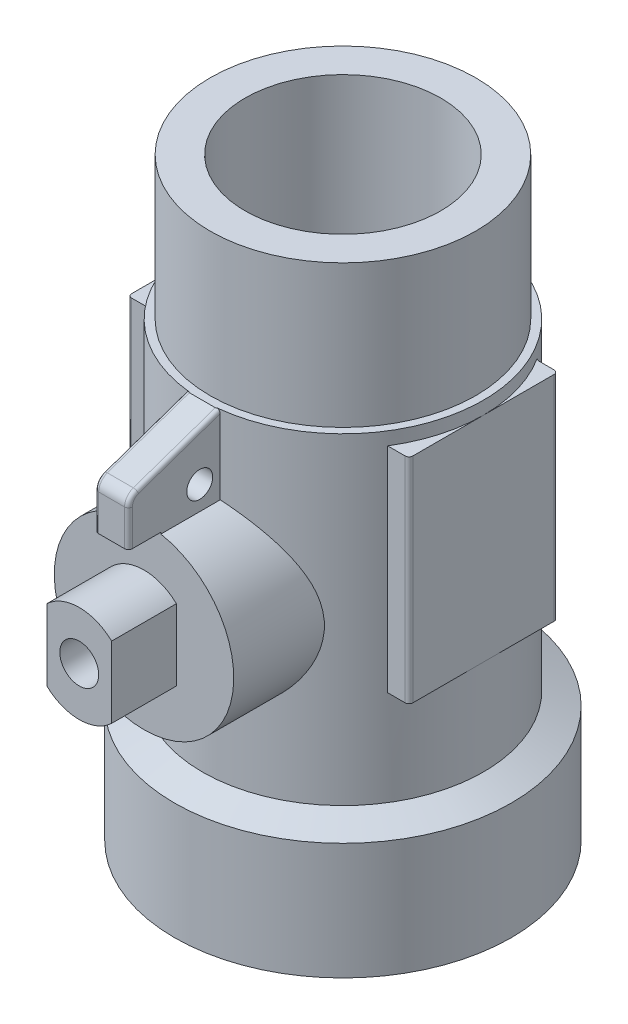
SolidWorks part; units mm, degrees
ref_plane "Front Plane" through (0, 0, 0) normal (0, 0, 1) x (1, 0, 0)
ref_plane "Top Plane" through (0, 0, 0) normal (0, 1, 0) x (1, 0, 0)
ref_plane "Right Plane" through (0, 0, 0) normal (1, 0, 0) x (0, 0, -1)
sketch "Sketch1" plane through (0, 0, 0) normal (0, 0, 1) x (1, 0, 0)
  line L0 (0, 0) -> (0, 45.85) construction
  line L1 (0, 45.85) -> (7.55, 45.85) construction
  line L2 (7.55, 45.85) -> (7.55, 33.85)
  line L3 (7.55, 33.85) -> (5, 32.85)
  line L4 (5, 32.85) -> (5, 28.85)
  line L5 (5, 28.85) -> (0, 28.85)
  line L6 (0, 28.85) -> (0, 12)
  line L7 (0, 12) -> (5, 12)
  line L8 (5, 12) -> (5, 7.7)
  line L9 (5, 7.7) -> (9, 7.7)
  line L10 (9, 7.7) -> (9, 0)
  line L11 (9, 0) -> (13, 0)
  line L12 (13, 0) -> (13, 9)
  line L13 (13, 9) -> (10.85, 10)
  line L16 (10.85, 10) -> (10.85, 34.85)
  line L20 (10.25, 34.85) -> (10.25, 45.85)
  line L21 (10.25, 45.85) -> (7.55, 45.85)
  line L22 (10.85, 34.85) -> (10.25, 34.85)
  point P13 (0, 0)
  point P18 (10.85, 10.0199)
  point P19 (0, 0)
  dimension "D1" = 45.85
  dimension "D2" = 12
  dimension "D3" = 13
  dimension "D4" = 17
  dimension "D5" = 10.25
  dimension "D6" = 2.7
  dimension "D7" = 5
  dimension "D8" = 11
  dimension "D9" = 8
  dimension "D10" = 1
  dimension "D11" = 13
  dimension "D12" = 4
  dimension "D14" = 7.7
  dimension "D15" = 12
  dimension "D16" = 10.85
  dimension "D17" = 9
revolve "Revolve1" add sketch "Sketch1" angle 360 about L0
ref_plane "Plane1" through (10.85, 0, 0) normal (1, 0, 0) x (0, 1, 0)
sketch "Sketch2" plane through (10.85, 0, 0) normal (1, 0, 0) x (0, 1, 0)
  line L1 (33.85, 5.75) -> (17.35, 5.75)
  line L2 (33.85, 5.75) -> (33.85, -5.75)
  line L3 (33.85, -5.75) -> (17.35, -5.75)
  line L4 (17.35, 5.75) -> (17.35, -5.75)
  line L5 (34.85, -10.85) -> (34.85, 10.85) construction
  point P4 (0, 0)
  point P7 (0, 0)
  point P8 (0, 0)
  point P10 (0, 0)
  point P12 (17.35, 0)
  dimension "D1" = 1
  dimension "D2" = 16.5
  dimension "D3" = 11.5
extrude "Boss-Extrude1" add sketch "Sketch2" against normal blind 2
mirror "Mirror1" about plane through (0, 0, 0) normal (1, 0, 0) of "Boss-Extrude1"
ref_plane "Plane2" through (0, 0, 10.85) normal (0, 0, 1) x (0, -1, 0)
sketch "Sketch3" plane through (0, 0, 10.85) normal (0, 0, 1) x (0, -1, 0)
  line L0 (0, -13) -> (0, 13) construction
  circle A0 centre (-22, 0) radius 6.925
  dimension "D1" = 13.85
  dimension "D2" = 22
extrude "Boss-Extrude2" add sketch "Sketch3" along normal blind 4.5 and the other way blind 3
sketch "Sketch4" plane through (0, 0, 0) normal (1, 0, 0) x (0, 0, -1)
  line L12 (-10.85, 34.85) -> (-17.85, 32.425)
  line L13 (-17.85, 32.425) -> (-17.85, 28.925)
  line L14 (-17.85, 28.925) -> (-15.35, 28.925)
  line L15 (-15.35, 28.925) -> (-15.35, 27.925)
  line L16 (-15.35, 27.925) -> (-10.25, 27.925)
  line L20 (-10.85, 34.85) -> (-10.25, 34.85)
  line L21 (-10.25, 34.85) -> (-10.25, 27.925)
  line L23 (10.85, 34.85) -> (-10.85, 34.85) construction
  line L24 (10.25, 34.85) -> (-10.25, 34.85) construction
  circle A0 centre (-12.35, 30.625) radius 1
  point P0 (-11.1968, 34.85)
  dimension "D6" = 2
  dimension "D1" = 2.5
  dimension "D2" = 3.5
  dimension "D3" = 1
  dimension "D4" = 2.7
  dimension "D5" = 2.1
extrude "Boss-Extrude6" add sketch "Sketch4" along normal blind 1.3 and the other way blind 1.3
fillet "Fillet2" radius 0.3 1 edges at (-9.2011, 25.6, 5.75)
fillet "Fillet4" radius 0.3 1 edges at (10.85, 25.6, 5.75)
fillet "Fillet7" radius 0.3 1 edges at (10.85, 25.6, -5.75)
fillet "Fillet8" radius 0.3 1 edges at (-10.85, 25.6, -5.75)
fillet "Fillet9" radius 0.3 1 edges at (-10.85, 25.6, 5.75)
fillet "Fillet10" radius 0.3 4 edges at (1.3, 30.675, 17.85) (-1.3, 33.6375, 14.35) (-1.3, 30.675, 17.85) (1.3, 33.6375, 14.35)
fillet "Fillet11" radius 0.3 1 edges at (9.2011, 25.6, -5.75)
fillet "Fillet12" radius 0.3 1 edges at (-9.2011, 25.6, -5.75)
sketch "Sketch5" plane through (0, 0, 15.35) normal (0, 0, 1) x (1, 0, 0)
  line L0 (-2.5, 19.25) -> (-2.5, 24.75)
  line L1 (2.5, 19.25) -> (2.5, 24.75)
  line L2 (-6.925, 22) -> (6.925, 22) construction
  line L3 (0, 15.075) -> (0, 28.925) construction
  line L4 (-1.3, 28.925) -> (1.3, 28.925) construction
  arc A0 (-2.5, 19.25) -> (2.5, 19.25) centre (0, 21.875) ccw
  arc A1 (-2.5, 24.75) -> (2.5, 24.75) centre (0, 22.125) cw
  circle A2 centre (0, 22) radius 1.5
  arc A3 (-1.3, 28.8019) -> (1.3, 28.8019) centre (0, 22) ccw construction
  point P6 (0, 18.25)
  point P7 (0, 25.75)
  point P14 (-2.5, 22)
  point P15 (2.5, 22)
  dimension "D4" = 3
  dimension "D1" = 5.5
  dimension "D2" = 7.5
  dimension "D3" = 5
extrude "Boss-Extrude7" add sketch "Sketch5" along normal blind 5
fillet "Fillet13" radius 1 3 edges at (1.2121, 32.3624, 17.7621) (-1.2121, 32.3624, 17.7621) (0, 32.425, 17.85)
